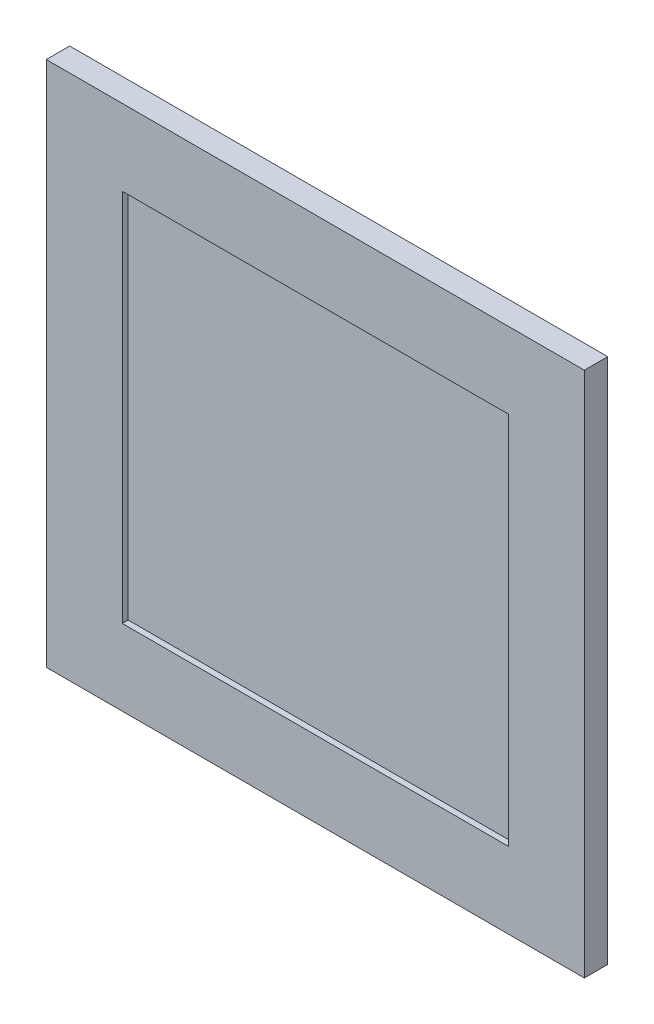
SolidWorks part; units mm, degrees
ref_plane "정면" through (0, 0, 0) normal (0, 0, 1) x (1, 0, 0)
ref_plane "윗면" through (0, 0, 0) normal (0, 1, 0) x (1, 0, 0)
ref_plane "우측면" through (0, 0, 0) normal (1, 0, 0) x (0, 0, -1)
sketch "스케치2" plane through (0, 0, 0) normal (0, 0, 1) x (1, 0, 0)
  line L1 (-230, 225) -> (230, 225)
  line L2 (-230, 225) -> (-230, -225)
  line L3 (-230, -225) -> (230, -225)
  line L4 (230, 225) -> (230, -225)
  line L5 (-230, 225) -> (230, -225) construction
  line L6 (-230, -225) -> (230, 225) construction
  point P0 (0, 0)
  dimension "92" = 460
  dimension "D2" = 450
extrude "보스-돌출1" add sketch "스케치2" along normal blind 20
sketch "스케치3" plane through (0, 0, 20) normal (0, 0, 1) x (1, 0, 0)
  line L5 (230, 225) -> (-230, 225) construction
  line L6 (-165, 160) -> (165, 160)
  line L7 (-165, 160) -> (-165, -160)
  line L9 (-165, -160) -> (165, -160)
  line L10 (165, 160) -> (165, -160)
  line L11 (-165, 160) -> (165, -160) construction
  line L12 (-165, -160) -> (165, 160) construction
  line L13 (230, -225) -> (230, 225) construction
  point P0 (0, 0)
  dimension "D1" = 65
  dimension "D2" = 65
extrude "컷-돌출1" cut sketch "스케치3" against normal blind 5
